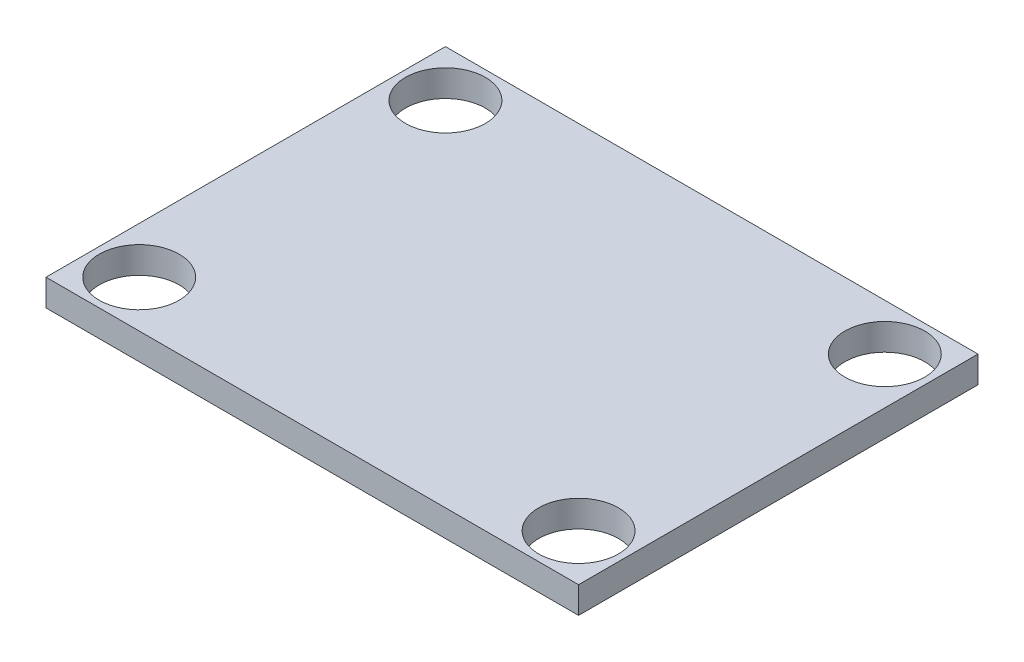
SolidWorks part; units mm, degrees
ref_plane "Front Plane" through (0, 0, 0) normal (0, 0, 1) x (1, 0, 0)
ref_plane "Top Plane" through (0, 0, 0) normal (0, 1, 0) x (1, 0, 0)
ref_plane "Right Plane" through (0, 0, 0) normal (1, 0, 0) x (0, 0, -1)
sketch "Sketch1" plane through (0, 0, 0) normal (0, 1, 0) x (1, 0, 0)
  line L0 (20, 30) -> (20, 0) construction
  line L1 (0, 0) -> (40, 0)
  line L2 (0, 0) -> (0, 30)
  line L3 (0, 30) -> (40, 30)
  line L4 (40, 0) -> (40, 30)
  line L5 (0, 15) -> (40, 15) construction
  circle A0 centre (3.5, 3.5) radius 3
  circle A1 centre (36.5, 3.5) radius 3
  circle A2 centre (36.5, 26.5) radius 3
  circle A3 centre (3.5, 26.5) radius 3
  dimension "D3" = 6
  dimension "D1" = 30
  dimension "D2" = 40
  dimension "D4" = 3.5
  dimension "D5" = 3.5
extrude "Boss-Extrude1" add sketch "Sketch1" along normal blind 2
